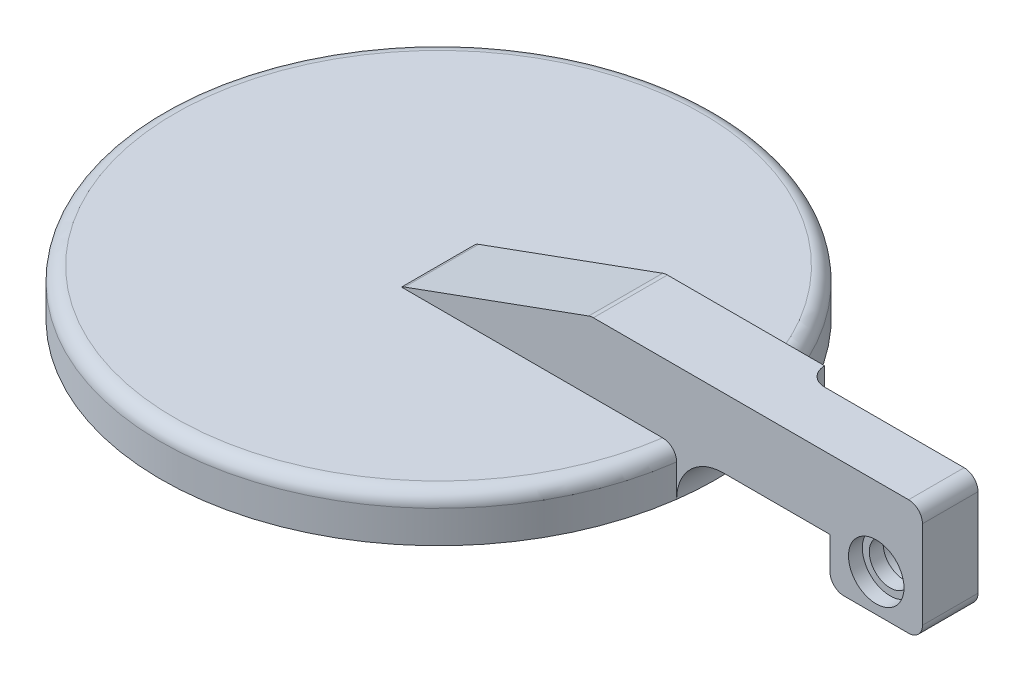
SolidWorks part; units mm, degrees
ref_plane "Front Plane" through (0, 0, 0) normal (0, 0, 1) x (1, 0, 0)
ref_plane "Top Plane" through (0, 0, 0) normal (0, 1, 0) x (1, 0, 0)
ref_plane "Right Plane" through (0, 0, 0) normal (1, 0, 0) x (0, 0, -1)
sketch "Sketch2" plane through (0, 0, 0) normal (0, 0, 1) x (1, 0, 0)
  line L7 (0, 0) -> (30, 0)
  line L8 (0, 0) -> (0, 5)
  line L9 (0, 5) -> (30, 5)
  line L10 (30, 0) -> (30, 5)
  dimension "D1" = 5
  dimension "D2" = 30
revolve "Revolve1" add sketch "Sketch2" angle 360 about L8
sketch "Sketch3" plane through (0, 5, 0) normal (0, 1, 0) x (1, 0, 0)
  line L0 (0, -10) -> (0, 10) construction
  line L1 (0, 10) -> (35, 10)
  line L2 (35, 10) -> (35, 6)
  line L3 (35, 6) -> (0, 6)
  line L4 (0, 10) -> (0, 6)
  line L5 (0, -10) -> (35, -10)
  line L6 (35, -10) -> (35, -6)
  line L7 (35, -6) -> (0, -6)
  line L8 (0, -6) -> (0, -10)
  line L9 (0, 4) -> (0, -4)
  line L10 (0, 4) -> (56.3, 4)
  line L11 (0, -4) -> (56.3, -4)
  line L12 (56.3, -4) -> (56.3, 4)
  point P4 (0, 0)
  point P13 (0, 0)
  circle M1 centre (0, 0) radius 30
  dimension "D1" = 20
  dimension "D2" = 35
  dimension "D3" = 4
  dimension "0.7" = 8
  dimension "D5" = 56.3
extrude "Boss-Extrude1" add sketch "Sketch3" along normal blind 7.5 contours L9 L11 L10 M1 | L11 L12 L10 M1 region at (14.9555, 5, 0) region at (43.1053, 5, 0)
sketch "Sketch4" plane through (0, 0, 0) normal (0, 0, 1) x (1, 0, 0)
  line L5 (35, 8.75) -> (37.8, 8.75) construction
  line L7 (56.3, 8.75) -> (37.8, 8.75) construction
  line L8 (56.3, 12.5) -> (56.3, 5) construction
  line L10 (-0.1339, 5) -> (20.4721, 12.5)
  line L11 (29.7321, 5) -> (-30, 5) construction
  line L12 (0, 12.5) -> (56.3, 12.5) construction
  line L13 (0, 5) -> (29.7321, 5) construction
  line L14 (20.4721, 12.5) -> (0, 12.5)
  line L15 (0, 12.5) -> (-0.1339, 5)
  circle A0 centre (37.8, 8.75) radius 2
  dimension "D3" = 4
  dimension "D1" = 20
  dimension "D2" = 18.5
extrude "Cut-Extrude1" cut sketch "Sketch4" against normal mid plane 30 contours L14 L15 L10
sketch "Sketch6" plane through (0, 5, 0) normal (0, -1, 0) x (1, 0, 0)
  line L6 (56.3, 4) -> (46.3, 4)
  line L7 (56.3, 4) -> (56.3, -4) construction
  line L8 (29.7321, 4) -> (56.3, 4) construction
  line L9 (46.3, 4) -> (46.3, -4)
  line L10 (29.7321, -4) -> (56.3, -4) construction
  line L11 (46.3, -4) -> (56.3, -4)
  line L12 (56.3, -4) -> (56.3, 4)
  dimension "D1" = 10
extrude "Boss-Extrude2" add sketch "Sketch6" along normal blind 5
sketch "Sketch7" plane through (0, 0, 4) normal (0, 0, 1) x (1, 0, 0)
  line L0 (51.3, 4) -> (51.3, 0) construction
  line L2 (56.3, 0) -> (46.3, 0) construction
  circle A0 centre (51.3, 4) radius 3
  dimension "D2" = 6
  dimension "D1" = 4
extrude "Cut-Extrude2" cut sketch "Sketch7" against normal blind 10
fillet "Fillet2" radius 1.5 6 edges at (46.3, 0, 0) (56.3, 0, 0) (56.3, 12.5, 0) (20.4721, 12.5, 0) (0, 5.0487, 0) (-30, 5, 0)
sketch "Sketch9" plane through (0, 0, -4) normal (0, 0, -1) x (-1, 0, 0)
  circle A0 centre (-51.3, 4) radius 3
  circle A1 centre (-51.3, 4) radius 4
  dimension "D1" = 6
  dimension "D2" = 8
sketch "Sketch10" plane through (0, 0, 4) normal (0, 0, 1) x (1, 0, 0)
  circle A0 centre (51.3, 4) radius 3.25
  circle A1 centre (51.3, 4) radius 2.25
  dimension "D1" = 6.5
  dimension "D2" = 4.5
extrude "Boss-Extrude4" add sketch "Sketch10" along normal blind 1.5 from offset 3 offset against normal yes
sketch "Sketch11" plane through (0, 0, 1) normal (0, 0, -1) x (-1, 0, 0)
  circle A0 centre (-51.3, 4) radius 2.6
  circle A1 centre (-51.3, 4) radius 3
  dimension "D1" = 5.2
  dimension "D2" = 6
sketch "Sketch12" plane through (0, 0, 0) normal (0, -1, 0) x (1, 0, 0)
  line L0 (0, 30) -> (0, 25.5) construction
  circle A0 centre (0, 0) radius 30 construction
  circle A1 centre (0, 27.75) radius 1.5
  circle A2 centre (19.6222, 19.6222) radius 1.5
  circle A3 centre (27.75, 0) radius 1.5
  circle A4 centre (19.6222, -19.6222) radius 1.5
  circle A5 centre (0, -27.75) radius 1.5
  circle A6 centre (-19.6222, -19.6222) radius 1.5
  circle A7 centre (-27.75, 0) radius 1.5
  circle A8 centre (-19.6222, 19.6222) radius 1.5
  point P24 (0, 0)
  dimension "D2" = 3
  dimension "D1" = 4.5
  dimension "D3" = 8
extrude "Cut-Extrude3" cut sketch "Sketch12" against normal blind 0.5
sketch "Sketch13" plane through (0, 5, 0) normal (0, -1, 0) x (1, 0, 0)
  line L0 (29.7321, -4) -> (37.7321, -4) construction
  line L1 (29.7321, -4) -> (46.3, -4) construction
  line L2 (37.7321, -4) -> (37.7321, -2)
  line L3 (37.7321, -2) -> (56.3, -2)
  line L4 (56.3, 4) -> (56.3, -4) construction
  line L5 (56.3, -2) -> (56.3, -4)
  line L6 (56.3, -4) -> (37.7321, -4)
  dimension "D1" = 8
  dimension "D2" = 2
extrude "Cut-Extrude4" cut sketch "Sketch13" against normal mid plane 15
fillet "Fillet3" radius 2 1 edges at (37.7321, 8.75, -2)
fillet "Fillet4" radius 5 1 edges at (30, 5, 0)
